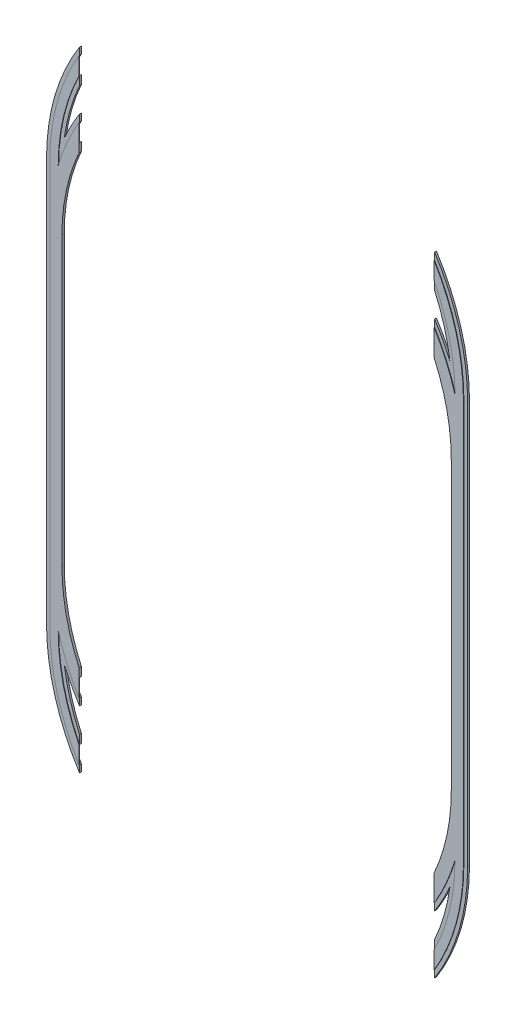
SolidWorks part; units mm, degrees
ref_plane "Front Plane" through (0, 0, 0) normal (0, 0, 1) x (1, 0, 0)
ref_plane "Top Plane" through (0, 0, 0) normal (0, 1, 0) x (1, 0, 0)
ref_plane "Right Plane" through (0, 0, 0) normal (1, 0, 0) x (0, 0, -1)
sketch "Sketch1" plane through (0, 0, 0) normal (0, 0, 1) x (1, 0, 0)
  line L0 (-1180.395, 1500.9938) -> (-1180.395, -1564.0062)
  line L1 (2985.905, 1500.9938) -> (2985.905, -1564.0062)
  line L2 (-1310.395, 2120.9938) -> (-1310.395, -2184.0062)
  line L3 (3115.905, 2120.9938) -> (3115.905, -2184.0062)
  line L4 (-1220.395, 1500.9938) -> (-1220.395, -1564.0062)
  line L5 (3025.905, 1500.9938) -> (3025.905, -1564.0062)
  line L6 (-1350.395, 2120.9938) -> (-1350.395, -2184.0062)
  line L7 (3155.905, 2120.9938) -> (3155.905, -2184.0062)
  arc A0 (2985.905, 1500.9938) -> (-1180.395, 1500.9938) centre (902.755, 1500.9938) ccw
  arc A1 (-1180.395, -1564.0062) -> (2985.905, -1564.0062) centre (902.755, -1564.0062) ccw
  arc A4 (3115.905, 2120.9938) -> (-1310.395, 2120.9938) centre (902.755, 2120.9938) ccw
  arc A5 (-1310.395, -2184.0062) -> (3115.905, -2184.0062) centre (902.755, -2184.0062) ccw
  arc A6 (3025.905, 1500.9938) -> (-1220.395, 1500.9938) centre (902.755, 1500.9938) ccw
  arc A7 (-1220.395, -1564.0062) -> (3025.905, -1564.0062) centre (902.755, -1564.0062) ccw
  arc A8 (-1350.395, -2184.0062) -> (3155.905, -2184.0062) centre (902.755, -2184.0062) ccw
  arc A9 (3155.905, 2120.9938) -> (-1350.395, 2120.9938) centre (902.755, 2120.9938) ccw
  dimension "D6" = 620
  dimension "D1" = 4166.3
  dimension "D2" = 3065
  dimension "D3" = 620
  dimension "D4" = 130
  dimension "D5" = 130
  dimension "D7" = 40
extrude "Boss-Extrude1" add sketch "Sketch1" along normal blind 20 contours L4 A7 L5 A6 A1 L0 A0 L1 | L7 A9 L6 A8 A5 L2 A4 L3 region at (902.755, 3615.6888, 0) region at (902.755, 4364.247, 0)
sketch "Sketch2" plane through (0, 0, 20) normal (0, 0, 1) x (1, 0, 0)
  line L0 (-1220.395, 2120.9938) -> (-1220.395, 2125.7073)
  line L1 (3025.905, 2120.9938) -> (3025.905, 2125.7073)
  line L2 (3025.905, -2184.0062) -> (3025.905, -2188.7198)
  line L3 (-1220.395, -2184.0062) -> (-1220.395, -2188.7198)
  arc A0 (3115.905, 2120.9938) -> (-1310.395, 2120.9938) centre (902.755, 2120.9938) ccw construction
  arc A1 (3025.905, 1500.9938) -> (-1220.395, 1500.9938) centre (902.755, 1500.9938) ccw construction
  arc A2 (3115.905, 2120.9938) -> (-1310.395, 2120.9938) centre (902.755, 2120.9938) ccw
  arc A3 (3025.905, 1500.9938) -> (-1220.395, 1500.9938) centre (902.755, 1500.9938) ccw
  arc A4 (3025.905, 2125.7073) -> (-1220.395, 2125.7073) centre (902.755, 1500.9938) ccw
  arc A5 (3025.905, 2120.9938) -> (-1220.395, 2120.9938) centre (902.755, 2120.9938) ccw
  arc A6 (2966.3872, 2405.4865) -> (-1160.8772, 2405.4865) centre (902.755, 1500.9938) ccw
  arc A7 (2966.3872, 2405.4865) -> (-1160.8772, 2405.4865) centre (902.755, 2120.9938) ccw
  arc A8 (3155.905, 1500.9938) -> (-1350.395, 1500.9938) centre (902.755, 1500.9938) ccw construction
  arc A9 (2985.905, 2120.9938) -> (-1180.395, 2120.9938) centre (902.755, 2120.9938) ccw construction
  arc A10 (3115.905, 1500.9938) -> (-1310.395, 1500.9938) centre (902.755, 1500.9938) ccw construction
  arc A11 (-1310.395, -2184.0062) -> (3115.905, -2184.0062) centre (902.755, -2184.0062) ccw construction
  arc A12 (-1220.395, -1564.0062) -> (3025.905, -1564.0062) centre (902.755, -1564.0062) ccw construction
  arc A13 (-1310.395, -2184.0062) -> (3115.905, -2184.0062) centre (902.755, -2184.0062) ccw
  arc A14 (-1220.395, -1564.0062) -> (3025.905, -1564.0062) centre (902.755, -1564.0062) ccw
  arc A15 (-1220.395, -2188.7198) -> (3025.905, -2188.7198) centre (902.755, -1564.0062) ccw
  arc A16 (-1220.395, -2184.0062) -> (3025.905, -2184.0062) centre (902.755, -2184.0062) ccw
  arc A17 (-1160.8772, -2468.499) -> (2966.3872, -2468.499) centre (902.755, -1564.0062) ccw
  arc A18 (-1160.8772, -2468.499) -> (2966.3872, -2468.499) centre (902.755, -2184.0062) ccw
  arc A19 (-1350.395, -1564.0062) -> (3155.905, -1564.0062) centre (902.755, -1564.0062) ccw construction
  arc A20 (-1180.395, -2184.0062) -> (2985.905, -2184.0062) centre (902.755, -2184.0062) ccw construction
  arc A21 (-1310.395, -1564.0062) -> (3115.905, -1564.0062) centre (902.755, -1564.0062) ccw construction
  dimension "D1" = 90
  dimension "D2" = 90
  dimension "D3" = 40
  dimension "D4" = 40
  dimension "D5" = 90
  dimension "D6" = 90
  dimension "D7" = 40
  dimension "D8" = 40
extrude "Boss-Extrude2" add sketch "Sketch2" against normal blind 20 separate body contours A15 A16 A18 A17 | A4 A5 A7 A6 region at (902.755, 4239.3984, 20) region at (902.755, -4302.4108, 20)
sketch "Sketch3" plane through (0, 0, 20) normal (0, 0, 1) x (1, 0, 0)
  line L0 (2985.905, 1500.9938) -> (2985.905, -1564.0062) construction
  line L1 (3155.905, 2120.9938) -> (3155.905, -2184.0062) construction
  line L2 (-1180.395, 1500.9938) -> (-1180.395, -1564.0062) construction
  line L3 (-1350.395, 2120.9938) -> (-1350.395, -2184.0062) construction
  line L4 (2985.905, 1500.9938) -> (2985.905, -1564.0062)
  line L5 (3155.905, 2120.9938) -> (3155.905, -2184.0062)
  line L6 (-1180.395, 1500.9938) -> (-1180.395, -1564.0062)
  line L7 (-1350.395, 2120.9938) -> (-1350.395, -2184.0062)
  line L10 (-1220.395, 2135.9938) -> (-1220.395, 2100.7073)
  arc A0 (-1350.395, -2184.0062) -> (3155.905, -2184.0062) centre (902.755, -2184.0062) ccw construction
  arc A1 (-1180.395, -1564.0062) -> (2985.905, -1564.0062) centre (902.755, -1564.0062) ccw construction
  arc A2 (2985.905, 1500.9938) -> (-1180.395, 1500.9938) centre (902.755, 1500.9938) ccw construction
  arc A3 (3155.905, 2120.9938) -> (-1350.395, 2120.9938) centre (902.755, 2120.9938) ccw construction
  arc A4 (-1350.395, -2184.0062) -> (3155.905, -2184.0062) centre (902.755, -2184.0062) ccw
  arc A5 (-1180.395, -1564.0062) -> (2985.905, -1564.0062) centre (902.755, -1564.0062) ccw
  arc A6 (2985.905, 1500.9938) -> (-1180.395, 1500.9938) centre (902.755, 1500.9938) ccw
  arc A7 (3155.905, 2120.9938) -> (-1350.395, 2120.9938) centre (902.755, 2120.9938) ccw
  arc A17 (3025.8997, 2125.7252) -> (-1220.3897, 2125.7252) centre (902.755, 2120.9938) ccw construction
  arc A18 (3025.8997, 2125.7252) -> (-1220.3897, 2125.7252) centre (902.755, 1500.9938) ccw construction
  arc A19 (3025.8997, 2125.7252) -> (-1220.3897, 2125.7252) centre (902.755, 2120.9938) ccw
  arc A20 (3025.8997, 2125.7252) -> (-1220.3897, 2125.7252) centre (902.755, 1500.9938) ccw
  arc A21 (-1220.3897, -2188.7377) -> (3025.8997, -2188.7377) centre (902.755, -2184.0062) ccw construction
  arc A22 (-1220.3897, -2188.7377) -> (3025.8997, -2188.7377) centre (902.755, -1564.0062) ccw construction
  arc A23 (-1220.3897, -2188.7377) -> (3025.8997, -2188.7377) centre (902.755, -2184.0062) ccw
  arc A24 (-1220.3897, -2188.7377) -> (3025.8997, -2188.7377) centre (902.755, -1564.0062) ccw
extrude "Boss-Extrude3" add sketch "Sketch3" along normal blind 5 contours A6 L4 A5 L6 A19 A20 region at (902.755, -4387.3671, 20)
ref_plane "Plane1" through (0, 4374.1438, 0) normal (0, 1, 0) x (1, 0, 0)
sketch "Sketch5" plane through (0, 4374.1438, 0) normal (0, 1, 0) x (1, 0, 0)
  line L0 (-1350.395, -10) -> (3155.905, -10)
  line L1 (-997.245, -298.271) -> (2802.755, -298.271)
  line L2 (-997.245, -298.271) -> (-997.245, 278.271)
  line L3 (-997.245, 278.271) -> (2802.755, 278.271)
  line L4 (2802.755, -298.271) -> (2802.755, 278.271)
  line L5 (-997.245, -298.271) -> (2802.755, 278.271) construction
  line L6 (-997.245, 278.271) -> (2802.755, -298.271) construction
  line L7 (-1350.395, -20) -> (-1350.395, 0) construction
  line L8 (3155.905, -20) -> (3155.905, 0) construction
  point P0 (902.755, -10)
  point P11 (0, 0)
  point P12 (902.755, -10)
  dimension "D1" = 3800
extrude "Cut-Extrude1" cut sketch "Sketch5" against normal through all contours L0 L4 L3 L2 | L1 L4 L0 L2 region at (902.755, 4374.1438, -134.1355) region at (902.755, 4374.1438, 154.1355)
sketch "Sketch7" plane through (0, 0, 20) normal (0, 0, -1) x (-1, 0, 0)
  line L1 (-2802.755, 3068.4989) -> (-2802.755, 3255.9092) construction
  line L2 (997.245, 3068.4989) -> (997.245, 3255.9092) construction
  circle A1 centre (-902.755, 2120.9937) radius 970.82
  point P5 (-2802.755, 3162.204)
  point P9 (997.245, 3162.204)
  point P14 (997.245, 2120.9937)
  dimension "D4" = 1941.64
